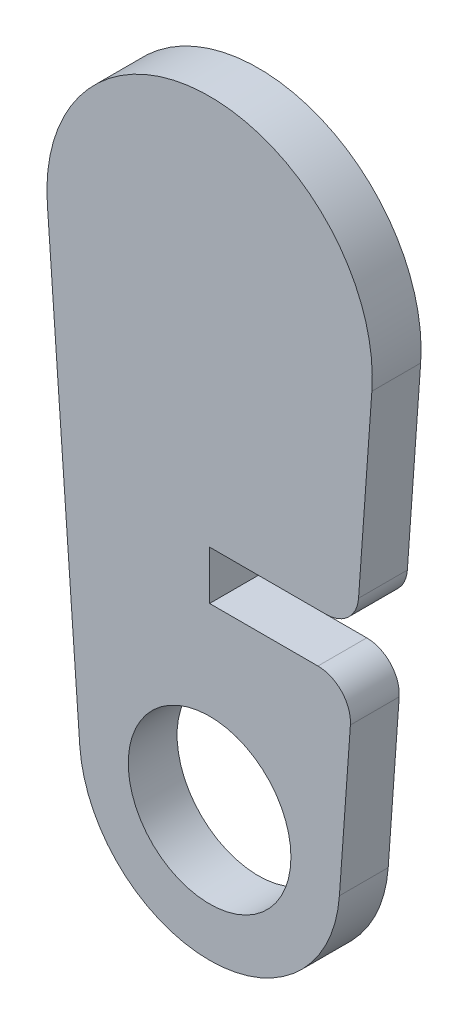
SolidWorks part; units mm, degrees
ref_plane "Plan de face" through (0, 0, 0) normal (0, 0, 1) x (1, 0, 0)
ref_plane "Plan de dessus" through (0, 0, 0) normal (0, 1, 0) x (1, 0, 0)
ref_plane "Plan de droite" through (0, 0, 0) normal (1, 0, 0) x (0, 0, -1)
sketch "Esquisse1" plane through (0, 0, 0) normal (0, 0, 1) x (1, 0, 0)
  line L0 (9.023, 14) -> (0, 14)
  line L1 (0, 14) -> (0, 11)
  line L2 (0, 11) -> (8.8082, 11)
  line L3 (0, 0) -> (0, 28) construction
  line L4 (-7.9796, -0.5714) -> (-9.9745, 27.2857)
  line L5 (9.9745, 27.2857) -> (7.9796, -0.5714) construction
  line L6 (9.9745, 27.2857) -> (9.023, 14)
  line L7 (8.8082, 11) -> (7.9796, -0.5714)
  circle A0 centre (0, 0) radius 5
  circle A1 centre (0, 28) radius 10 construction
  arc A2 (-9.9745, 27.2857) -> (9.9745, 27.2857) centre (0, 28) cw
  arc A3 (-7.9796, -0.5714) -> (7.9796, -0.5714) centre (0, 0) ccw
  dimension "D1" = 10
  dimension "D4" = 10
  dimension "D6" = 3
  dimension "D2" = 3
  dimension "D3" = 14
  dimension "D7" = 28
extrude "Boss.-Extru.1" add sketch "Esquisse1" along normal blind 3
fillet "Congé1" radius 2 2 edges at (8.8082, 11, 1.5) (9.023, 14, 1.5)
